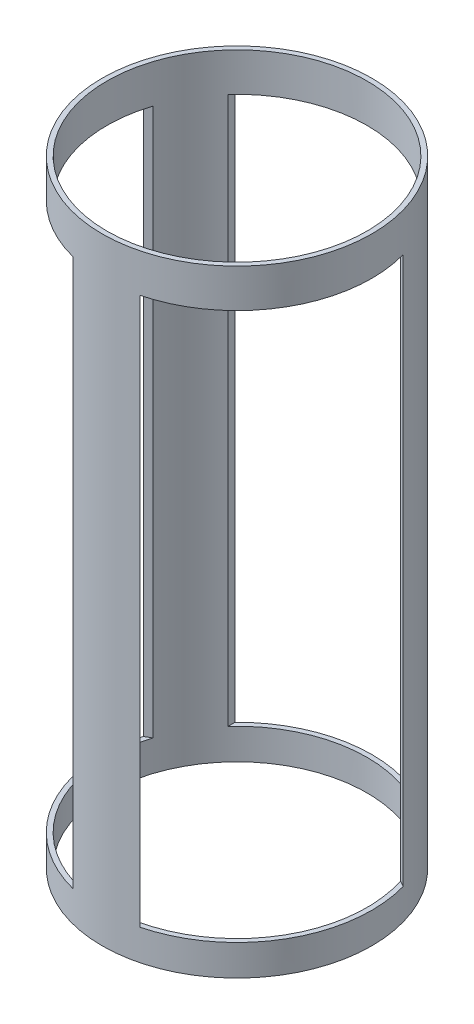
SolidWorks part; units mm, degrees
material "6061-T6 (SS)"
ref_plane "Front Plane" through (0, 0, 0) normal (0, 0, 1) x (1, 0, 0)
ref_plane "Top Plane" through (0, 0, 0) normal (0, 1, 0) x (1, 0, 0)
ref_plane "Right Plane" through (0, 0, 0) normal (1, 0, 0) x (0, 0, -1)
sketch "Sketch1" plane through (0, 0, 0) normal (0, 1, 0) x (1, 0, 0)
  circle A0 centre (0, 0) radius 88.9
  circle A1 centre (0, 0) radius 85.725
  dimension "D1" = 177.8
  dimension "D2" = 171.45
extrude "Boss-Extrude1" add sketch "Sketch1" along normal mid plane 406.4
sketch "Sketch2" plane through (0, 0, 0) normal (0, 0, 1) x (1, 0, 0)
  line L0 (85.725, 203.2) -> (-85.725, 203.2) construction
  line L1 (-63.5, -182.88) -> (63.5, -182.88)
  line L2 (-63.5, -182.88) -> (-63.5, 177.8)
  line L3 (-63.5, 177.8) -> (63.5, 177.8)
  line L4 (63.5, -182.88) -> (63.5, 177.8)
  line L5 (-63.5, -182.88) -> (63.5, 177.8) construction
  line L6 (-63.5, 177.8) -> (63.5, -182.88) construction
  line L7 (88.9, -203.2) -> (88.9, 203.2) construction
  line L8 (-88.9, 203.2) -> (-88.9, -203.2) construction
  line L9 (-88.9, -203.2) -> (88.9, -203.2) construction
  point P0 (0, 0)
  dimension "D1" = 25.4
  dimension "D2" = 25.4
  dimension "D3" = 25.4
  dimension "D4" = 20.32
extrude "Cut-Extrude1" cut sketch "Sketch2" against normal up to surface (62.217 mm away) up to face at (0, 203.2, 88.9)
pattern_circular "CirPattern1" count 3 over 360 about axis through (0, 203.2, 0) along (0, -1, 0) of "Cut-Extrude1"
ref_plane "Plane1" through (88.9, 0, 0) normal (1, 0, 0) x (0, 0, -1)
sketch "Sketch3" plane through (88.9, 0, 0) normal (1, 0, 0) x (0, 0, -1)
  line L0 (23.8841, -182.88) -> (-86.1011, -182.88) construction
  line L1 (-88.9, -203.2) -> (88.9, -203.2) construction
  circle A0 centre (0, -199.39) radius 1.4351
  circle A1 centre (0, -189.23) radius 1.4351
  dimension "D1" = 3.81
  dimension "D2" = 2.8702
  dimension "D3" = 2.8702
  dimension "D4" = 6.35
extrude "Cut-Extrude2" [suppressed] cut sketch "Sketch3" against normal blind 15.24
pattern_circular "CirPattern2" [suppressed] count 12 over 360 reverse direction yes of bodies 104
sketch "Sketch4" plane through (88.9, 0, 0) normal (1, 0, 0) x (0, 0, -1)
  line L0 (0, 97.79) -> (0, -97.79) construction
  line L1 (88.9, 203.2) -> (-88.9, 203.2) construction
  circle A0 centre (0, 196.85) radius 1.4351
  dimension "D1" = 2.8702
  dimension "D2" = 6.35
extrude "Cut-Extrude3" [suppressed] cut sketch "Sketch4" against normal blind 15.24
pattern_circular "CirPattern3" [suppressed] count 12 over 360 of bodies 107
ref_plane "Plane2" through (0, 0, 88.9) normal (0, 0, 1) x (1, 0, 0)
sketch "Sketch5" [suppressed] plane through (0, 0, 88.9) normal (0, 0, 1) x (1, 0, 0)
  circle A0 centre (0, 68.1736) radius 1.4351
  circle A1 centre (0, -60.5536) radius 1.4351
  circle A2 centre (0, 196.85) radius 1.4351 construction
  circle A3 centre (0, -189.23) radius 1.4351 construction
  dimension "D1" = 128.6764
  dimension "D2" = 128.6764
  dimension "D3" = 2.8702
  dimension "D4" = 2.8702
extrude "Cut-Extrude4" [suppressed] cut sketch "Sketch5" against normal blind 35.56
pattern_circular "CirPattern4" [suppressed] count 3 over 360 of bodies 109
